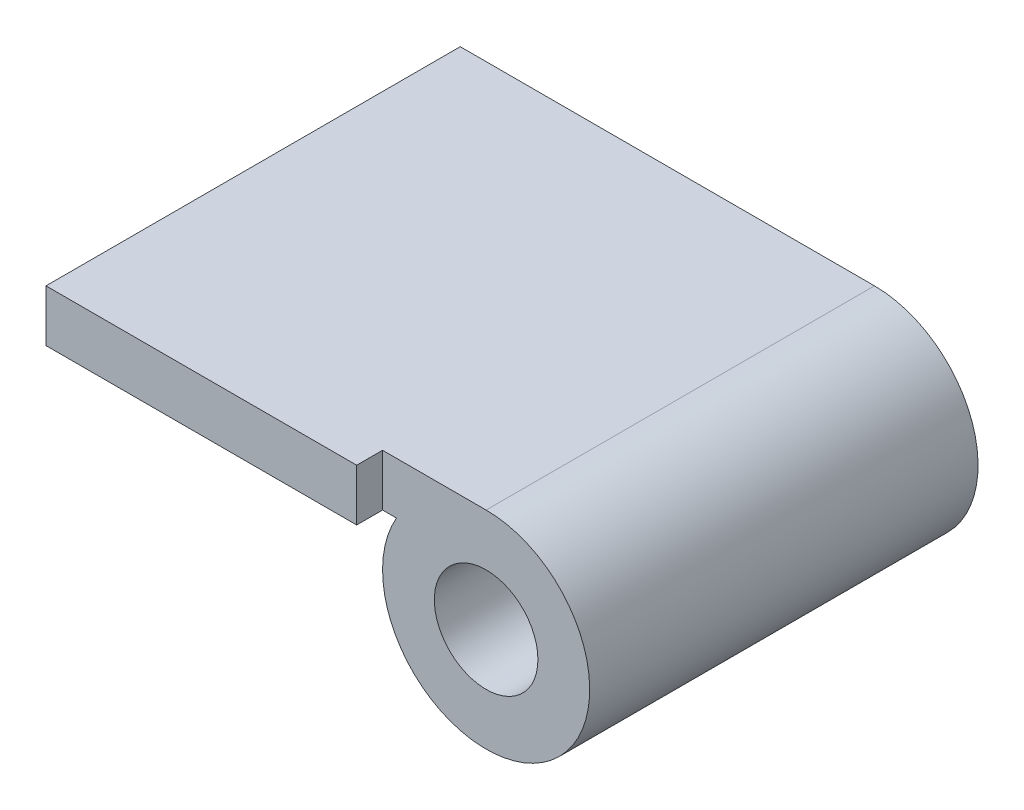
SolidWorks part; units mm, degrees
ref_plane "Front Plane" through (0, 0, 0) normal (0, 0, 1) x (1, 0, 0)
ref_plane "Top Plane" through (0, 0, 0) normal (0, 1, 0) x (1, 0, 0)
ref_plane "Right Plane" through (0, 0, 0) normal (1, 0, 0) x (0, 0, -1)
sketch "Sketch1" plane through (0, 0, 0) normal (0, 0, 1) x (1, 0, 0)
  line L1 (0, 3.175) -> (-25.4, 3.175)
  line L2 (-25.4, 3.175) -> (-25.4, 6.35)
  line L3 (-25.4, 6.35) -> (0, 6.35)
  circle A0 centre (0, 0) radius 6.35
  circle A1 centre (0, 0) radius 3.175
  dimension "D1" = 6.35
  dimension "D2" = 12.7
  dimension "D3" = 25.4
extrude "Boss-Extrude1" add sketch "Sketch1" along normal blind 25.4 contours A0 L3 L2 L1 | A1 A0 region at (-3.0852, 5.3437, 0) region at (-14.613, 4.8143, 0)
sketch "Sketch2" plane through (0, 0, 25.4) normal (0, 0, 1) x (1, 0, 0)
  line L0 (-25.4, 6.35) -> (0, 6.35) construction
  line L1 (6.35, -6.35) -> (-6.35, -6.35)
  line L2 (6.35, -6.35) -> (6.35, 6.35)
  line L3 (6.35, 6.35) -> (-6.35, 6.35)
  line L4 (-6.35, -6.35) -> (-6.35, 6.35)
  line L5 (6.35, -6.35) -> (-6.35, 6.35) construction
  line L6 (6.35, 6.35) -> (-6.35, -6.35) construction
  arc A0 (-5.4993, 3.175) -> (0, 6.35) centre (0, 0) ccw construction
  point P0 (0, 0)
extrude "Cut-Extrude1" cut sketch "Sketch2" against normal blind 1.5875
